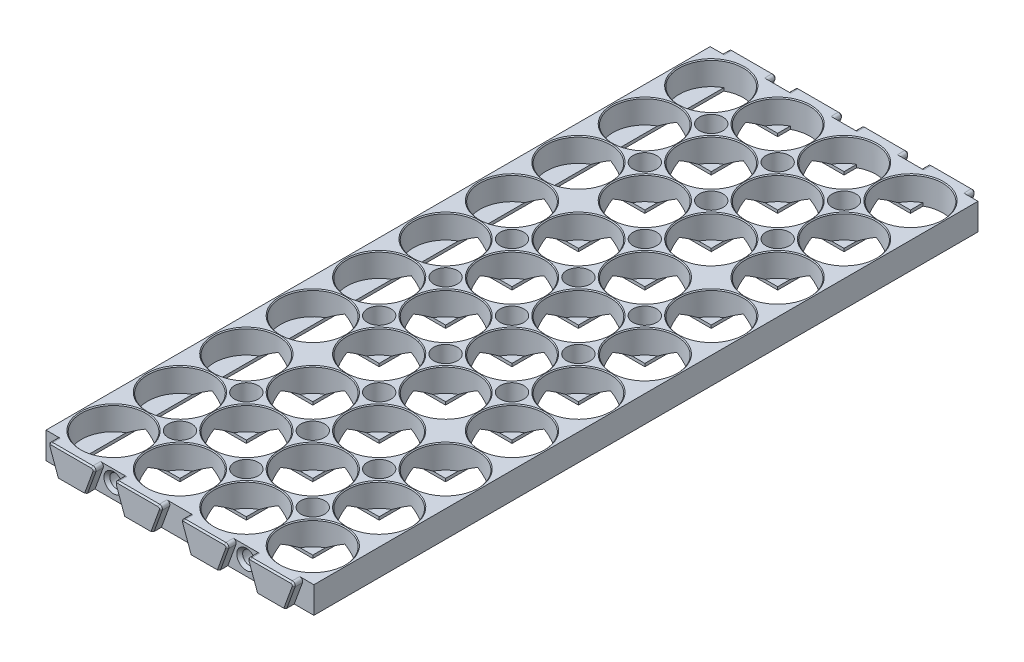
SolidWorks part; units mm, degrees
ref_plane "Front Plane" through (0, 0, 0) normal (0, 0, 1) x (1, 0, 0)
ref_plane "Top Plane" through (0, 0, 0) normal (0, 1, 0) x (1, 0, 0)
ref_plane "Right Plane" through (0, 0, 0) normal (1, 0, 0) x (0, 0, -1)
sketch "Sketch1" plane through (0, 0, 0) normal (0, 1, 0) x (1, 0, 0)
  line L0 (-11.25, 10.875) -> (11.25, 10.875) construction
  line L1 (-11.25, -11.25) -> (11.25, -11.25)
  line L2 (-11.25, -11.25) -> (-11.25, 11.25)
  line L3 (-11.25, 11.25) -> (11.25, 11.25)
  line L4 (11.25, -11.25) -> (11.25, 11.25)
  line L5 (-11.25, -11.25) -> (11.25, 11.25) construction
  line L6 (-11.25, 11.25) -> (11.25, -11.25) construction
  circle A0 centre (0, 0) radius 10.875
  point P0 (0, 0)
  dimension "D1" = 21.75
  dimension "D2" = 22.5
  dimension "D3" = 0.375
extrude "Boss-Extrude1" add sketch "Sketch1" along normal blind 8
sketch "Sketch2" plane through (0, 0, 0) normal (0, -1, 0) x (1, 0, 0)
  line L0 (5.25, 11.25) -> (-5.25, 11.25) construction
  line L1 (11.25, 11.25) -> (5.25, 11.25)
  line L2 (11.25, 11.25) -> (11.25, 5.25)
  line L3 (11.25, 5.25) -> (5.25, 5.25)
  line L4 (5.25, 11.25) -> (5.25, 5.25)
  line L5 (11.25, -11.25) -> (5.25, -11.25)
  line L6 (11.25, -11.25) -> (11.25, -5.25)
  line L7 (11.25, -5.25) -> (5.25, -5.25)
  line L8 (5.25, -11.25) -> (5.25, -5.25)
  line L9 (-11.25, -11.25) -> (-5.25, -11.25)
  line L10 (-11.25, -11.25) -> (-11.25, -5.25)
  line L11 (-11.25, -5.25) -> (-5.25, -5.25)
  line L12 (-5.25, -11.25) -> (-5.25, -5.25)
  line L13 (-11.25, 11.25) -> (-5.25, 11.25)
  line L14 (-11.25, 11.25) -> (-11.25, 5.25)
  line L15 (-11.25, 5.25) -> (-5.25, 5.25)
  line L16 (-5.25, 11.25) -> (-5.25, 5.25)
  line L17 (11.25, 5.25) -> (11.25, -5.25) construction
  line L18 (5.25, -11.25) -> (-5.25, -11.25) construction
  line L19 (-11.25, 5.25) -> (-11.25, -5.25) construction
  dimension "D1" = 10.5
extrude "Boss-Extrude2" add sketch "Sketch2" along normal blind 1
chamfer "Chamfer2" distance 0.3 angle 45 1 edges at (0, 8, 10.875)
pattern_linear "LPattern1" count 10 spacing 22.5 along (0, 0, 1) count 4 spacing 22.5 along (1, 0, 0) of "Boss-Extrude2", "Boss-Extrude1", "Chamfer2"
sketch "Sketch5" plane through (0, 0, -5.25) normal (0, 0, 1) x (1, 0, 0)
  line L0 (72.75, -1) -> (72.75, 0) construction
  line L20 (78.75, -1) -> (72.75, -1) construction
  line L25 (-5.25, -1) -> (-5.25, 0) construction
  line L26 (-5.25, -1) -> (-11.25, -1) construction
  line L27 (-11.25, -1) -> (-11.25, 0) construction
  line L29 (-5.25, 0) -> (-9.5238, 0) construction
  line L35 (-5.25, -1) -> (-5.25, 0)
  line L36 (-5.25, -1) -> (-11.25, -1)
  line L37 (-11.25, -1) -> (-11.25, 0)
  line L39 (-5.25, 0) -> (-11.25, 0)
  line L46 (78.75, -1) -> (78.75, 0) construction
  line L47 (78.75, 0) -> (77.0238, 0) construction
  line L48 (77.0238, 0) -> (72.75, 0) construction
  line L49 (72.75, -1) -> (72.75, 0)
  line L50 (78.75, -1) -> (72.75, -1)
  line L51 (78.75, -1) -> (78.75, 0)
  line L52 (78.75, 0) -> (77.0238, 0)
  line L53 (77.0238, 0) -> (72.75, 0)
  dimension "D1" = 6
extrude "Boss-Extrude3" add sketch "Sketch5" along normal up to surface (219 mm away)
sketch "Sketch6" plane through (0, 0, 0) normal (0, -1, 0) x (1, 0, 0)
  line L24 (62.25, -11.25) -> (72.75, -11.25) construction
  line L25 (72.75, -11.25) -> (72.75, -9.5238) construction
  line L26 (62.25, -9.5238) -> (62.25, -11.25) construction
  line L27 (39.75, -11.25) -> (50.25, -11.25) construction
  line L28 (50.25, -11.25) -> (50.25, -9.5238) construction
  line L29 (39.75, -9.5238) -> (39.75, -11.25) construction
  line L30 (17.25, -9.5238) -> (17.25, -11.25) construction
  line L31 (17.25, -11.25) -> (27.75, -11.25) construction
  line L32 (27.75, -11.25) -> (27.75, -9.5238) construction
  line L33 (-5.25, -9.5238) -> (-5.25, -11.25) construction
  line L34 (-5.25, -11.25) -> (5.25, -11.25) construction
  line L35 (5.25, -11.25) -> (5.25, -9.5238) construction
  line L48 (62.25, -11.25) -> (72.75, -11.25)
  line L49 (72.75, -11.25) -> (72.75, -9.5238)
  line L50 (62.25, -9.5238) -> (62.25, -11.25)
  line L51 (39.75, -11.25) -> (50.25, -11.25)
  line L52 (50.25, -11.25) -> (50.25, -9.5238)
  line L53 (39.75, -9.5238) -> (39.75, -11.25)
  line L54 (17.25, -9.5238) -> (17.25, -11.25)
  line L55 (17.25, -11.25) -> (27.75, -11.25)
  line L56 (27.75, -11.25) -> (27.75, -9.5238)
  line L57 (-5.25, -9.5238) -> (-5.25, -11.25)
  line L58 (-5.25, -11.25) -> (5.25, -11.25)
  line L59 (5.25, -11.25) -> (5.25, -9.5238)
  line L108 (72.75, 212.0238) -> (72.75, 213.75) construction
  line L109 (72.75, 213.75) -> (62.25, 213.75) construction
  line L110 (62.25, 213.75) -> (62.25, 212.0238) construction
  line L111 (50.25, 212.0238) -> (50.25, 213.75) construction
  line L112 (50.25, 213.75) -> (39.75, 213.75) construction
  line L113 (39.75, 213.75) -> (39.75, 212.0238) construction
  line L114 (27.75, 212.0238) -> (27.75, 213.75) construction
  line L115 (27.75, 213.75) -> (17.25, 213.75) construction
  line L116 (17.25, 213.75) -> (17.25, 212.0238) construction
  line L117 (5.25, 213.75) -> (-5.25, 213.75) construction
  line L118 (-5.25, 213.75) -> (-5.25, 212.0238) construction
  line L119 (5.25, 212.0238) -> (5.25, 213.75) construction
  line L120 (72.75, 212.0238) -> (72.75, 213.75)
  line L121 (72.75, 213.75) -> (62.25, 213.75)
  line L122 (62.25, 213.75) -> (62.25, 212.0238)
  line L123 (50.25, 212.0238) -> (50.25, 213.75)
  line L124 (50.25, 213.75) -> (39.75, 213.75)
  line L125 (39.75, 213.75) -> (39.75, 212.0238)
  line L126 (27.75, 212.0238) -> (27.75, 213.75)
  line L127 (27.75, 213.75) -> (17.25, 213.75)
  line L128 (17.25, 213.75) -> (17.25, 212.0238)
  line L129 (5.25, 213.75) -> (-5.25, 213.75)
  line L130 (-5.25, 213.75) -> (-5.25, 212.0238)
  line L131 (5.25, 212.0238) -> (5.25, 213.75)
  arc A8 (62.25, -9.5238) -> (72.75, -9.5238) centre (67.5, 0) ccw construction
  arc A9 (39.75, -9.5238) -> (50.25, -9.5238) centre (45, 0) ccw construction
  arc A10 (17.25, -9.5238) -> (27.75, -9.5238) centre (22.5, 0) ccw construction
  arc A11 (-5.25, -9.5238) -> (5.25, -9.5238) centre (0, 0) ccw construction
  arc A16 (62.25, -9.5238) -> (72.75, -9.5238) centre (67.5, 0) ccw
  arc A17 (39.75, -9.5238) -> (50.25, -9.5238) centre (45, 0) ccw
  arc A18 (17.25, -9.5238) -> (27.75, -9.5238) centre (22.5, 0) ccw
  arc A19 (-5.25, -9.5238) -> (5.25, -9.5238) centre (0, 0) ccw
  arc A36 (72.75, 212.0238) -> (62.25, 212.0238) centre (67.5, 202.5) ccw construction
  arc A37 (50.25, 212.0238) -> (39.75, 212.0238) centre (45, 202.5) ccw construction
  arc A38 (27.75, 212.0238) -> (17.25, 212.0238) centre (22.5, 202.5) ccw construction
  arc A39 (5.25, 212.0238) -> (-5.25, 212.0238) centre (0, 202.5) ccw construction
  arc A40 (72.75, 212.0238) -> (62.25, 212.0238) centre (67.5, 202.5) ccw
  arc A41 (50.25, 212.0238) -> (39.75, 212.0238) centre (45, 202.5) ccw
  arc A42 (27.75, 212.0238) -> (17.25, 212.0238) centre (22.5, 202.5) ccw
  arc A43 (5.25, 212.0238) -> (-5.25, 212.0238) centre (0, 202.5) ccw
extrude "Boss-Extrude4" add sketch "Sketch6" along normal up to surface (1 mm away) up to face at (-8.25, -1, 101.25)
sketch "Sketch7" plane through (0, 0, 0) normal (0, 0, 1) x (1, 0, 0)
  line L1 (-5.25, 0) -> (5.25, 0)
  line L2 (-5.25, 0) -> (0, 5.25) construction
  line L3 (0, 5.25) -> (5.25, 0) construction
  line L4 (0, 0) -> (0, 8) construction
  line L5 (-11.25, 8) -> (78.75, 8) construction
  line L6 (-5.25, 0) -> (0, 3.0311)
  line L7 (0, 3.0311) -> (5.25, 0)
  line L9 (-5.25, -1) -> (-5.25, 0) construction
  line L10 (5.25, -1) -> (5.25, 0) construction
  line L11 (-5.25, -1) -> (-5.25, 0) construction
  line L12 (5.25, -1) -> (5.25, 0) construction
  line L13 (17.25, 0) -> (22.5, 3.0311)
  line L14 (22.5, 3.0311) -> (27.75, 0)
  line L15 (17.25, 0) -> (27.75, 0)
  line L16 (39.75, 0) -> (45, 3.0311)
  line L17 (45, 3.0311) -> (50.25, 0)
  line L18 (39.75, 0) -> (50.25, 0)
  line L19 (62.25, 0) -> (67.5, 3.0311)
  line L20 (67.5, 3.0311) -> (72.75, 0)
  line L21 (62.25, 0) -> (72.75, 0)
  line L22 (-5.25, 0) -> (17.25, 0) construction
  dimension "D1" = 45
  dimension "D2" = 30
  dimension "D3" = 4.9689
  dimension "D5" = 22.5
  dimension "D4" = 4
extrude "Cut-Extrude1" cut sketch "Sketch7" along normal up to surface (207.75 mm away) up to face at (11.25, -0.3333, 207.75)
sketch "Sketch16" plane through (0, 0, 0) normal (1, 0, 0) x (0, 0, -1)
  line L2 (-5.25, -1) -> (-5.25, 0) construction
  line L3 (5.25, -1) -> (5.25, 0) construction
  line L4 (-5.25, 0) -> (0, 3.0311)
  line L5 (0, 3.0311) -> (5.25, 0)
  line L6 (-5.25, 0) -> (5.25, 0)
  line L7 (-5.25, -1) -> (-5.25, 0) construction
  line L8 (5.25, -1) -> (5.25, 0) construction
  line L9 (-22.5, 3.0311) -> (-17.25, 0)
  line L10 (-27.75, 0) -> (-17.25, 0)
  line L11 (-27.75, 0) -> (-22.5, 3.0311)
  line L12 (-45, 3.0311) -> (-39.75, 0)
  line L13 (-50.25, 0) -> (-39.75, 0)
  line L14 (-50.25, 0) -> (-45, 3.0311)
  line L15 (-67.5, 3.0311) -> (-62.25, 0)
  line L16 (-72.75, 0) -> (-62.25, 0)
  line L17 (-72.75, 0) -> (-67.5, 3.0311)
  line L18 (-90, 3.0311) -> (-84.75, 0)
  line L19 (-95.25, 0) -> (-84.75, 0)
  line L20 (-95.25, 0) -> (-90, 3.0311)
  line L21 (-112.5, 3.0311) -> (-107.25, 0)
  line L22 (-117.75, 0) -> (-107.25, 0)
  line L23 (-117.75, 0) -> (-112.5, 3.0311)
  line L24 (-135, 3.0311) -> (-129.75, 0)
  line L25 (-140.25, 0) -> (-129.75, 0)
  line L26 (-140.25, 0) -> (-135, 3.0311)
  line L27 (-157.5, 3.0311) -> (-152.25, 0)
  line L28 (-162.75, 0) -> (-152.25, 0)
  line L29 (-162.75, 0) -> (-157.5, 3.0311)
  line L30 (-180, 3.0311) -> (-174.75, 0)
  line L31 (-185.25, 0) -> (-174.75, 0)
  line L32 (-185.25, 0) -> (-180, 3.0311)
  line L33 (-202.5, 3.0311) -> (-197.25, 0)
  line L34 (-207.75, 0) -> (-197.25, 0)
  line L35 (-207.75, 0) -> (-202.5, 3.0311)
  line L36 (-225, 3.0311) -> (-219.75, 0)
  line L37 (-230.25, 0) -> (-219.75, 0)
  line L38 (-230.25, 0) -> (-225, 3.0311)
  line L39 (-247.5, 3.0311) -> (-242.25, 0)
  line L40 (-252.75, 0) -> (-242.25, 0)
  line L41 (-252.75, 0) -> (-247.5, 3.0311)
  line L42 (0, 3.0311) -> (-22.5, 3.0311) construction
  dimension "D1" = 30
  dimension "D3" = 22.5
  dimension "D2" = 12
extrude "Cut-Extrude7" cut sketch "Sketch16" along normal up to surface (62.25 mm away) up to face at (62.25, -0.3333, 11.25)
sketch "Sketch8" plane through (0, 0, -11.25) normal (0, 0, -1) x (-1, 0, 0)
  line L0 (0, -1) -> (0, 8) construction
  line L1 (-27.4743, -1) -> (-30.75, 8)
  line L2 (-78.75, 8) -> (11.25, 8) construction
  line L3 (4.9743, -1) -> (-4.9743, -1)
  line L4 (-4.9743, -1) -> (-8.25, 8)
  line L5 (-8.25, 8) -> (8.25, 8)
  line L6 (4.9743, -1) -> (8.25, 8)
  line L7 (11.25, 8) -> (11.25, -1) construction
  line L8 (11.25, -1) -> (-78.75, -1) construction
  line L9 (-30.75, 8) -> (-14.25, 8)
  line L10 (-78.75, 8) -> (11.25, 8) construction
  line L11 (-17.5257, -1) -> (-14.25, 8)
  line L12 (-17.5257, -1) -> (-27.4743, -1)
  line L13 (-49.9743, -1) -> (-53.25, 8)
  line L14 (-53.25, 8) -> (-36.75, 8)
  line L15 (-40.0257, -1) -> (-36.75, 8)
  line L16 (-40.0257, -1) -> (-49.9743, -1)
  line L17 (-72.4743, -1) -> (-75.75, 8)
  line L18 (-75.75, 8) -> (-59.25, 8)
  line L19 (-62.5257, -1) -> (-59.25, 8)
  line L20 (-62.5257, -1) -> (-72.4743, -1)
  line L21 (-4.9743, -1) -> (-27.4743, -1) construction
  line L22 (-78.75, 8) -> (11.25, 8) construction
  dimension "D1" = 70
  dimension "D2" = 3
  dimension "D4" = 22.5
  dimension "D5" = 9
  dimension "D3" = 4
sketch "Sketch9" plane through (0, 0, 213.75) normal (0, 0, 1) x (1, 0, 0)
  line L24 (-4.9743, -1) -> (4.9743, -1)
  line L25 (4.9743, -1) -> (8.25, 8)
  line L26 (8.25, 8) -> (-8.25, 8)
  line L27 (-8.25, 8) -> (-4.9743, -1)
  line L28 (-4.9743, -1) -> (4.9743, -1)
  line L29 (4.9743, -1) -> (8.25, 8)
  line L30 (8.25, 8) -> (-8.25, 8)
  line L31 (-8.25, 8) -> (-4.9743, -1)
  line L32 (72.4743, -1) -> (75.75, 8)
  line L33 (75.75, 8) -> (59.25, 8)
  line L34 (59.25, 8) -> (62.5257, -1)
  line L35 (62.5257, -1) -> (72.4743, -1)
  line L36 (72.4743, -1) -> (75.75, 8)
  line L37 (75.75, 8) -> (59.25, 8)
  line L38 (59.25, 8) -> (62.5257, -1)
  line L39 (62.5257, -1) -> (72.4743, -1)
  line L40 (49.9743, -1) -> (53.25, 8)
  line L41 (53.25, 8) -> (36.75, 8)
  line L42 (36.75, 8) -> (40.0257, -1)
  line L43 (40.0257, -1) -> (49.9743, -1)
  line L44 (49.9743, -1) -> (53.25, 8)
  line L45 (53.25, 8) -> (36.75, 8)
  line L46 (36.75, 8) -> (40.0257, -1)
  line L47 (40.0257, -1) -> (49.9743, -1)
  line L48 (14.25, 8) -> (17.5257, -1)
  line L49 (17.5257, -1) -> (27.4743, -1)
  line L50 (27.4743, -1) -> (30.75, 8)
  line L51 (30.75, 8) -> (14.25, 8)
  line L52 (14.25, 8) -> (17.5257, -1)
  line L53 (17.5257, -1) -> (27.4743, -1)
  line L54 (27.4743, -1) -> (30.75, 8)
  line L55 (30.75, 8) -> (14.25, 8)
  dimension "D1" = 0
  dimension "D2" = 0
  dimension "D3" = 0
  dimension "D4" = 0
extrude "Boss-Extrude5" add sketch "Sketch8" along normal blind 3
extrude "Boss-Extrude6" add sketch "Sketch9" along normal blind 3
fillet "Fillet1" radius 1 16 edges at (-8.25, 8, 215.25) (8.25, 8, 215.25) (14.25, 8, 215.25) (30.75, 8, 215.25) (36.75, 8, 215.25) (53.25, 8, 215.25) (59.25, 8, 215.25) (75.75, 8, 215.25) (75.75, 8, -12.75) (59.25, 8, -12.75) (53.25, 8, -12.75) (36.75, 8, -12.75) (30.75, 8, -12.75) (14.25, 8, -12.75) (8.25, 8, -12.75) (-8.25, 8, -12.75)
chamfer "Chamfer3" distance 0.5 angle 45 40 edges at (6.3679, 2.829, -14.25) (0, 8, -14.25) (-6.3679, 2.829, -14.25) (73.8679, 2.829, -14.25) (67.5, 8, -14.25) (61.1321, 2.829, -14.25) (51.3679, 2.829, -14.25) (45, 8, -14.25) (38.6321, 2.829, -14.25) (28.8679, 2.829, -14.25) (22.5, 8, -14.25) (16.1321, 2.829, -14.25) (73.8679, 2.829, 216.75) (61.1321, 2.829, 216.75) (67.5, 8, 216.75) (51.3679, 2.829, 216.75) (38.6321, 2.829, 216.75) (45, 8, 216.75) (28.8679, 2.829, 216.75) (16.1321, 2.829, 216.75) (22.5, 8, 216.75) (6.3679, 2.829, 216.75) (-6.3679, 2.829, 216.75) (0, 8, 216.75) (75.141, 7.5736, 216.75) (59.859, 7.5736, 216.75) (52.641, 7.5736, 216.75) (37.359, 7.5736, 216.75) (30.141, 7.5736, 216.75) (14.859, 7.5736, 216.75) (7.641, 7.5736, 216.75) (-7.641, 7.5736, 216.75) (75.141, 7.5736, -14.25) (59.859, 7.5736, -14.25) (52.641, 7.5736, -14.25) (37.359, 7.5736, -14.25) (30.141, 7.5736, -14.25) (14.859, 7.5736, -14.25) (7.641, 7.5736, -14.25) (-7.641, 7.5736, -14.25)
sketch "Sketch10" plane through (0, 0, -11.25) normal (0, 0, -1) x (-1, 0, 0)
  line L0 (-11.25, -1) -> (-11.25, 8) construction
  line L2 (-4.9743, -1) -> (-17.5257, -1) construction
  line L4 (-14.25, 8) -> (-8.25, 8) construction
  line L5 (-33.75, 8) -> (-33.75, -1) construction
  line L6 (-36.75, 8) -> (-30.75, 8) construction
  line L7 (-27.4743, -1) -> (-40.0257, -1) construction
  circle A0 centre (-11.25, 4) radius 2.25
  circle A1 centre (-56.25, 4) radius 2.25
  dimension "D2" = 4.5
  dimension "D1" = 4
sketch "Sketch11" plane through (0, 0, 213.75) normal (0, 0, 1) x (1, 0, 0)
  circle A0 centre (11.25, 4) radius 2.25 construction
  circle A1 centre (11.25, 4) radius 2.25
  circle A2 centre (56.25, 4) radius 2.25 construction
  circle A3 centre (56.25, 4) radius 2.25
extrude "Cut-Extrude2" cut sketch "Sketch10" against normal blind 5
extrude "Cut-Extrude3" cut sketch "Sketch11" against normal blind 5
chamfer "Chamfer5" distance 1 angle 45 4 edges at (58.5, 4, -11.25) (9, 4, -11.25) (13.5, 4, 213.75) (58.5, 4, 213.75)
sketch "Sketch17" plane through (0, -1, 0) normal (0, -1, 0) x (1, 0, 0)
  line L0 (5.25, 5.25) -> (17.25, 17.25) construction
  line L1 (11.25, 11.25) -> (33.75, 11.25) construction
  line L2 (5.25, 185.25) -> (17.25, 197.25) construction
  circle A0 centre (11.25, 11.25) radius 4
  circle A1 centre (33.75, 11.25) radius 4
  circle A2 centre (56.25, 11.25) radius 4
  circle A33 centre (33.75, 146.25) radius 4 [skipped]
  circle A34 centre (56.25, 146.25) radius 4 [skipped]
  circle A35 centre (33.75, 168.75) radius 4 [skipped]
  circle A36 centre (33.75, 191.25) radius 4 [skipped]
  circle A37 centre (56.25, 191.25) radius 4 [skipped]
  circle A38 centre (33.75, 213.75) radius 4 [skipped]
  circle A39 centre (56.25, 213.75) radius 4 [skipped]
  circle A40 centre (33.75, 236.25) radius 4 [skipped]
  circle A41 centre (56.25, 236.25) radius 4 [skipped]
  circle A42 centre (11.25, 146.25) radius 4 [skipped]
  circle A43 centre (11.25, 191.25) radius 4 [skipped]
  circle A44 centre (11.25, 213.75) radius 4 [skipped]
  circle A45 centre (11.25, 236.25) radius 4 [skipped]
  circle A46 centre (56.25, 168.75) radius 4 construction
  circle A47 centre (11.25, 168.75) radius 4 construction
  circle A48 centre (33.75, 123.75) radius 4 [skipped]
  circle A49 centre (56.25, 123.75) radius 4 [skipped]
  circle A50 centre (11.25, 123.75) radius 4 [skipped]
  circle A57 centre (33.75, 33.75) radius 4 [skipped]
  circle A58 centre (33.75, 56.25) radius 4 [skipped]
  circle A59 centre (56.25, 56.25) radius 4 [skipped]
  circle A60 centre (33.75, 78.75) radius 4 [skipped]
  circle A61 centre (56.25, 78.75) radius 4 [skipped]
  circle A62 centre (33.75, 101.25) radius 4 [skipped]
  circle A63 centre (56.25, 101.25) radius 4 [skipped]
  circle A64 centre (11.25, 56.25) radius 4 [skipped]
  circle A65 centre (11.25, 78.75) radius 4 [skipped]
  circle A66 centre (11.25, 101.25) radius 4 [skipped]
  circle A67 centre (56.25, 33.75) radius 4 construction
  circle A68 centre (11.25, 33.75) radius 4 construction
  circle A87 centre (11.25, 258.75) radius 4 [skipped]
  circle A88 centre (33.75, 258.75) radius 4 [skipped]
  circle A89 centre (56.25, 258.75) radius 4 [skipped]
  circle A90 centre (11.25, 281.25) radius 4 [skipped]
  circle A91 centre (33.75, 281.25) radius 4 [skipped]
  circle A92 centre (56.25, 281.25) radius 4 [skipped]
  circle A93 centre (11.25, 33.75) radius 4
  circle A94 centre (33.75, 33.75) radius 4
  circle A95 centre (56.25, 33.75) radius 4
  circle A96 centre (11.25, 56.25) radius 4 construction
  circle A97 centre (33.75, 56.25) radius 4
  circle A98 centre (56.25, 56.25) radius 4 construction
  circle A99 centre (11.25, 78.75) radius 4
  circle A100 centre (33.75, 78.75) radius 4
  circle A101 centre (56.25, 78.75) radius 4
  circle A102 centre (11.25, 101.25) radius 4
  circle A103 centre (33.75, 101.25) radius 4
  circle A104 centre (56.25, 101.25) radius 4
  circle A105 centre (11.25, 123.75) radius 4
  circle A106 centre (33.75, 123.75) radius 4
  circle A107 centre (56.25, 123.75) radius 4
  circle A108 centre (11.25, 146.25) radius 4 construction
  circle A109 centre (33.75, 146.25) radius 4
  circle A110 centre (56.25, 146.25) radius 4 construction
  circle A111 centre (11.25, 168.75) radius 4
  circle A112 centre (33.75, 168.75) radius 4
  circle A113 centre (56.25, 168.75) radius 4
  circle A114 centre (11.25, 191.25) radius 4
  circle A115 centre (33.75, 191.25) radius 4
  circle A116 centre (56.25, 191.25) radius 4
  dimension "D4" = 22.5
  dimension "D5" = 9
  dimension "D1" = 8
  dimension "D3" = 13
extrude "Cut-Extrude8" cut sketch "Sketch17" against normal through all
sketch "Sketch18" plane through (0, -1, 0) normal (0, -1, 0) x (1, 0, 0)
  line L1 (50.25, 129.75) -> (50.25, 117.75) construction
  line L2 (5.25, 140.25) -> (17.25, 152.25) construction
  line L3 (5.25, 50.25) -> (17.25, 62.25) construction
  line L4 (50.25, 50.25) -> (62.25, 62.25) construction
  line L5 (50.25, 50.25) -> (62.25, 50.25) construction
  line L6 (50.25, 62.25) -> (50.25, 50.25) construction
  line L38 (78.75, 101.25) -> (-11.25, 101.25) construction
  line L39 (78.75, -11.25) -> (78.75, 213.75) construction
  line L40 (-11.25, 213.75) -> (-11.25, -11.25) construction
  line L42 (50.25, 140.25) -> (62.25, 152.25) construction
  circle A0 centre (11.25, 56.25) radius 2.1
  circle A4 centre (56.25, 56.25) radius 2.1
  circle A7 centre (56.25, 146.25) radius 2.1
  circle A8 centre (11.25, 146.25) radius 2.1
  dimension "D1" = 4.2
extrude "Cut-Extrude9" cut sketch "Sketch18" against normal blind 4
sketch "Sketch19" plane through (0, -1, 0) normal (0, -1, 0) x (1, 0, 0)
  line L0 (78.75, 101.25) -> (-11.25, 101.25) construction
  line L1 (78.75, -11.25) -> (78.75, 213.75) construction
  line L2 (-11.25, 213.75) -> (-11.25, -11.25) construction
  circle A2 centre (56.25, 146.25) radius 1.7
  circle A3 centre (11.25, 56.25) radius 1.7
  circle A4 centre (11.25, 146.25) radius 1.7
  circle A5 centre (56.25, 56.25) radius 1.7
  dimension "D1" = 3.4
extrude "Cut-Extrude10" cut sketch "Sketch19" against normal offset from surface (7 mm away) 2 up to face at (11.25, 8, 187.25)
chamfer "Chamfer6" distance 1 angle 45 4 edges at (11.25, -1, 144.15) (56.25, -1, 144.15) (11.25, -1, 54.15) (56.25, -1, 54.15)
sketch "Sketch22" plane through (0, 8, 0) normal (0, 1, 0) x (1, 0, 0)
  line L1 (-11.25, 11.25) -> (-11.625, 11.25)
  line L2 (-11.25, 11.25) -> (-11.25, -213.75)
  line L3 (-11.25, -213.75) -> (-11.625, -213.75)
  line L4 (-11.625, 11.25) -> (-11.625, -213.75)
  line L5 (33.75, 11.25) -> (33.75, -213.75) construction
  line L6 (36.75, 11.25) -> (30.75, 11.25) construction
  line L12 (30.75, -213.75) -> (36.75, -213.75) construction
  line L13 (-11.25, -213.75) -> (-6.8219, -213.75) construction
  line L14 (79.125, 11.25) -> (79.125, -213.75)
  line L15 (78.75, -213.75) -> (79.125, -213.75)
  line L16 (78.75, 11.25) -> (78.75, -213.75)
  line L17 (78.75, 11.25) -> (79.125, 11.25)
  arc A1 (-5.25, 9.5238) -> (-5.25, -9.5238) centre (0, 0) ccw construction
  point P10 (-10.875, 0)
  dimension "D1" = 0.75
  dimension "D2" = 0.375
extrude "Boss-Extrude7" add sketch "Sketch22" against normal up to surface (9 mm away) up to face at (33.75, -1, 101.25)
sketch "Sketch14" plane through (0, -1, 0) normal (0, -1, 0) x (1, 0, 0)
  line L0 (33.75, -11.25) -> (33.75, 213.75) construction
  line L2 (27.4743, -11.25) -> (40.0257, -11.25) construction
  line L3 (40.0257, 213.75) -> (27.4743, 213.75) construction
  line L4 (39.75, 129.75) -> (27.75, 129.75) construction
  line L19 (-5.25, 11.25) -> (-11.625, 11.25) construction
  line L39 (-5.25, 9.5238) -> (-5.25, 12.9762) construction
  line L40 (-11.625, -11.25) -> (-11.625, 213.75) construction
  line L51 (-6.25, 10.25) -> (-6.25, 12.25)
  line L55 (-10.25, 8.7941) -> (-10.25, 13.7059)
  line L56 (-5.25, -9.5238) -> (-5.25, 212.0238) construction
  line L57 (-10.25, 13.7059) -> (-6.25, 12.25)
  line L59 (33.75, 129.75) -> (33.75, 117.75) construction
  line L60 (-5.25, 191.25) -> (-11.625, 191.25) construction
  line L61 (27.75, 117.75) -> (39.75, 117.75) construction
  line L69 (-11.625, 101.25) -> (-5.25, 101.25) construction
  line L70 (-6.25, 100.25) -> (-6.25, 102.25)
  line L71 (-10.25, 98.7941) -> (-10.25, 103.7059)
  line L75 (-10.25, 8.7941) -> (-6.25, 10.25)
  line L76 (-10.25, 103.7059) -> (-6.25, 102.25)
  line L77 (-10.25, 193.7059) -> (-6.25, 192.25)
  line L78 (-10.25, 188.7941) -> (-6.25, 190.25)
  line L79 (-10.25, 193.7059) -> (-10.25, 188.7941)
  line L84 (-6.25, 192.25) -> (-6.25, 190.25)
  line L85 (79.125, 101.25) -> (72.75, 101.25) construction
  line L86 (72.75, 191.25) -> (79.125, 191.25) construction
  line L87 (72.75, 11.25) -> (79.125, 11.25) construction
  line L93 (77.75, 98.7941) -> (73.75, 100.25)
  line L94 (73.75, 192.25) -> (73.75, 190.25)
  line L95 (77.75, 193.7059) -> (77.75, 188.7941)
  line L98 (-10.25, 98.7941) -> (-6.25, 100.25)
  line L100 (77.75, 188.7941) -> (73.75, 190.25)
  line L101 (77.75, 193.7059) -> (73.75, 192.25)
  line L102 (77.75, 103.7059) -> (73.75, 102.25)
  line L103 (77.75, 8.7941) -> (73.75, 10.25)
  line L104 (77.75, 98.7941) -> (77.75, 103.7059)
  line L105 (73.75, 100.25) -> (73.75, 102.25)
  line L106 (77.75, 13.7059) -> (73.75, 12.25)
  line L107 (77.75, 8.7941) -> (77.75, 13.7059)
  line L108 (73.75, 10.25) -> (73.75, 12.25)
  point P17 (-6.25, 11.25)
  point P18 (-10.25, 11.25)
  point P24 (-10.25, 101.25)
  point P25 (-6.25, 101.25)
  point P32 (-10.25, 191.25)
  point P35 (-6.25, 191.25)
  point P56 (73.75, 191.25)
  point P57 (77.75, 191.25)
  point P58 (73.75, 101.25)
  point P59 (77.75, 101.25)
  point P60 (77.75, 11.25)
  point P61 (73.75, 11.25)
  dimension "D1" = 70
  dimension "D2" = 1.375
  dimension "D3" = 4
  dimension "D4" = 1
  dimension "D5" = 70
  dimension "D7" = 1
  dimension "D8" = 4
extrude "Cut-Extrude11" cut sketch "Sketch14" against normal blind 2
chamfer "Chamfer7" distance 0.5 angle 45 24 edges at (-10.25, -1, 191.25) (-8.25, -1, 189.5221) (-6.25, -1, 191.25) (-8.25, -1, 192.9779) (73.75, -1, 191.25) (75.75, -1, 189.5221) (77.75, -1, 191.25) (75.75, -1, 192.9779) (73.75, -1, 101.25) (75.75, -1, 99.5221) (77.75, -1, 101.25) (75.75, -1, 102.9779) (-6.25, -1, 101.25) (-8.25, -1, 99.5221) (-10.25, -1, 101.25) (-8.25, -1, 102.9779) (75.75, -1, 9.5221) (77.75, -1, 11.25) (73.75, -1, 11.25) (75.75, -1, 12.9779) (-6.25, -1, 11.25) (-8.25, -1, 9.5221) (-10.25, -1, 11.25) (-8.25, -1, 12.9779)
equation "\"cell_side\"= 22.50"
equation "\"D2@Sketch1\"=\"cell_side\""
equation "\"D5@Sketch7\"=\"cell_side\""
equation "\"D3@Sketch16\"=\"cell_side\""
equation "\"D4@Sketch8\"=\"cell_side\""
equation "\"D3@LPattern1\"=\"cell_side\""
equation "\"D4@LPattern1\"=\"cell_side\""
equation "\"D4@Sketch17\"=\"cell_side\""
